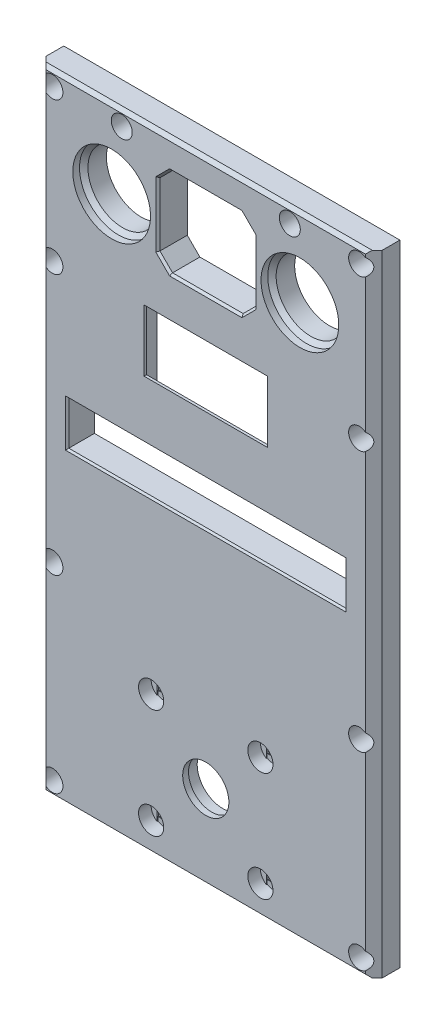
SolidWorks part; units mm, degrees
ref_plane "Front Plane" through (0, 0, 0) normal (0, 0, 1) x (1, 0, 0)
ref_plane "Top Plane" through (0, 0, 0) normal (0, 1, 0) x (1, 0, 0)
ref_plane "Right Plane" through (0, 0, 0) normal (1, 0, 0) x (0, 0, -1)
sketch "Sketch1" plane through (0, 0, 0) normal (0, 0, 1) x (1, 0, 0)
  line L1 (-40, -75) -> (40, -75)
  line L2 (-40, -75) -> (-40, 75)
  line L3 (-40, 75) -> (40, 75)
  line L4 (40, -75) -> (40, 75)
  line L5 (-40, -75) -> (40, 75) construction
  line L6 (-40, 75) -> (40, -75) construction
  line L7 (-33, -68) -> (33, -68)
  line L8 (-33, -68) -> (-33, 68)
  line L9 (-33, 68) -> (33, 68)
  line L10 (33, -68) -> (33, 68)
  line L11 (-33, -68) -> (33, 68) construction
  line L12 (-33, 68) -> (33, -68) construction
  point P0 (0, 0)
  point P6 (0, 0)
  dimension "D1" = 150
  dimension "D2" = 80
  dimension "D3" = 7
  dimension "D4" = 7
extrude "Boss-Extrude1" add sketch "Sketch1" along normal blind 7
sketch "Sketch2" plane through (0, 0, 7) normal (0, 0, 1) x (1, 0, 0)
  line L0 (33, -68) -> (33, 68) construction
  line L1 (-33, -68) -> (33, -68)
  line L2 (-33, -68) -> (-33, -32)
  line L3 (-33, -32) -> (33, -32)
  line L4 (33, -68) -> (33, -32)
  dimension "D1" = 36
extrude "Boss-Extrude2" add sketch "Sketch2" against normal up to surface (7 mm away) up to face at (0, 0, 0)
sketch "Sketch3" plane through (0, 0, 0) normal (0, 0, -1) x (-1, 0, 0)
  line L0 (0, -75) -> (0, -55) construction
  line L1 (40, -75) -> (-40, -75) construction
  circle A0 centre (0, -55) radius 5.5
  dimension "D1" = 11
  dimension "D2" = 20
extrude "Cut-Extrude1" cut sketch "Sketch3" against normal through all
sketch "Sketch4" plane through (0, 0, 0) normal (0, 0, -1) x (-1, 0, 0)
  circle A0 centre (0, -55) radius 6.05
  dimension "D1" = 12.1
extrude "Cut-Extrude2" cut sketch "Sketch4" against normal offset from surface (5.6 mm away) 1.4 up to face at (-5.5, -55, 7)
sketch "Sketch5" plane through (0, 0, 0) normal (0, 0, -1) x (-1, 0, 0)
  circle A0 centre (0, -55) radius 11.1
  dimension "D1" = 22.2
extrude "Cut-Extrude3" cut sketch "Sketch5" against normal offset from surface (3 mm away) 2.6 up to face at (-6.05, -55, 5.6)
sketch "Sketch6" plane through (0, 0, 0) normal (0, 0, -1) x (-1, 0, 0)
  line L1 (-13, -68) -> (13, -68) construction
  line L2 (-13, -68) -> (-13, -42) construction
  line L3 (-13, -42) -> (13, -42) construction
  line L4 (13, -68) -> (13, -42) construction
  line L5 (-13, -68) -> (13, -42) construction
  line L6 (-13, -42) -> (13, -68) construction
  circle A0 centre (-13, -42) radius 1.6
  circle A1 centre (13, -42) radius 1.6
  circle A2 centre (13, -68) radius 1.6
  circle A3 centre (-13, -68) radius 1.6
  point P0 (0, -55)
  dimension "D2" = 3.2
  dimension "D1" = 26
extrude "Cut-Extrude4" cut sketch "Sketch6" against normal through all
sketch "Sketch7" plane through (0, 0, 0) normal (0, 0, -1) x (-1, 0, 0)
  line L1 (-25, -74) -> (25, -74)
  line L2 (-25, -74) -> (-25, -36)
  line L3 (-25, -36) -> (25, -36)
  line L4 (25, -74) -> (25, -36)
  line L5 (-25, -74) -> (25, -36) construction
  line L6 (-25, -36) -> (25, -74) construction
  point P0 (0, -55)
  dimension "D1" = 50
  dimension "D2" = 38
extrude "Cut-Extrude5" cut sketch "Sketch7" against normal blind 1
sketch "Sketch8" plane through (0, 0, 7) normal (0, 0, 1) x (1, 0, 0)
  circle A0 centre (-13, -42) radius 3
  circle A1 centre (13, -42) radius 3
  circle A2 centre (13, -68) radius 3
  circle A3 centre (-13, -68) radius 3
  dimension "D1" = 6
extrude "Cut-Extrude6" cut sketch "Sketch8" against normal blind 3
sketch "Sketch9" plane through (0, 0, 7) normal (0, 0, 1) x (1, 0, 0)
  line L0 (-40, 75) -> (-40, -75) construction
  line L1 (-36.5, -71.5) -> (36.5, -71.5) construction
  line L2 (-36.5, -71.5) -> (-36.5, 71.5) construction
  line L3 (-36.5, 71.5) -> (36.5, 71.5) construction
  line L4 (36.5, -71.5) -> (36.5, 71.5) construction
  line L5 (-36.5, -71.5) -> (36.5, 71.5) construction
  line L6 (-36.5, 71.5) -> (36.5, -71.5) construction
  line L7 (40, 75) -> (-40, 75) construction
  circle A0 centre (-36.5, 71.5) radius 1.35
  circle A1 centre (36.5, 71.5) radius 1.35
  circle A2 centre (36.5, -71.5) radius 1.35
  circle A3 centre (-36.5, -71.5) radius 1.35
  circle A6 centre (-36.5, 35.5) radius 1.35
  circle A7 centre (-36.5, -26.5) radius 1.35
  circle A8 centre (36.5, -26.5) radius 1.35
  circle A9 centre (36.5, 35.5) radius 1.35
  point P0 (0, 0)
  dimension "D3" = 2.7
  dimension "D4" = 45
  dimension "D5" = 36
  dimension "D1" = 3.5
  dimension "D2" = 3.5
extrude "Cut-Extrude7" cut sketch "Sketch9" against normal through all
sketch "Sketch10" plane through (0, 0, 7) normal (0, 0, 1) x (1, 0, 0)
  circle A0 centre (-36.5, 71.5) radius 2.5
  circle A1 centre (36.5, 71.5) radius 2.5
  circle A2 centre (-36.5, 35.5) radius 2.5
  circle A3 centre (-36.5, -26.5) radius 2.5
  circle A4 centre (-36.5, -71.5) radius 2.5
  circle A5 centre (36.5, -71.5) radius 2.5
  circle A6 centre (36.5, 35.5) radius 2.5
  circle A7 centre (36.5, -26.5) radius 2.5
  dimension "D1" = 5
extrude "Cut-Extrude8" cut sketch "Sketch10" against normal blind 5
chamfer "Chamfer1" distance 2 angle 45 2 edges at (-40, 0, 7) (40, 0, 7)
sketch "Sketch11" plane through (0, 0, 7) normal (0, 0, 1) x (1, 0, 0)
  line L0 (33, -32) -> (33, 68) construction
  line L1 (-33, -32) -> (33, -32)
  line L2 (-33, -32) -> (-33, -1.5)
  line L3 (-33, -1.5) -> (33, -1.5)
  line L4 (33, -32) -> (33, -1.5)
  line L5 (-38, -75) -> (38, -75) construction
  dimension "D1" = 73.5
extrude "Boss-Extrude3" add sketch "Sketch11" against normal up to surface (7 mm away) up to face at (37.85, 71.5, 0)
sketch "Sketch12" plane through (0, 0, 2) normal (0, 0, 1) x (1, 0, 0)
  line L2 (-37.85, -73.6042) -> (-37.85, -69.3958)
  line L4 (-35.15, -73.6042) -> (-35.15, -69.3958)
  line L5 (-37.85, -73.6042) -> (-35.15, -69.3958) construction
  line L6 (-37.85, -69.3958) -> (-35.15, -73.6042) construction
  line L8 (-37.85, -28.6042) -> (-37.85, -24.3958)
  line L10 (-35.15, -28.6042) -> (-35.15, -24.3958)
  line L11 (-37.85, -28.6042) -> (-35.15, -24.3958) construction
  line L12 (-37.85, -24.3958) -> (-35.15, -28.6042) construction
  line L14 (-37.85, 33.3958) -> (-37.85, 37.6042)
  line L16 (-35.15, 33.3958) -> (-35.15, 37.6042)
  line L17 (-37.85, 33.3958) -> (-35.15, 37.6042) construction
  line L18 (-37.85, 37.6042) -> (-35.15, 33.3958) construction
  line L20 (-37.85, 69.3958) -> (-37.85, 73.6042)
  line L22 (-35.15, 69.3958) -> (-35.15, 73.6042)
  line L23 (-37.85, 69.3958) -> (-35.15, 73.6042) construction
  line L24 (-37.85, 73.6042) -> (-35.15, 69.3958) construction
  arc A0 (-38, -73.5) -> (-38, -69.5) centre (-36.5, -71.5) ccw construction
  circle A1 centre (-36.5, -26.5) radius 2.5 construction
  circle A2 centre (-36.5, 35.5) radius 2.5 construction
  arc A3 (-38, 69.5) -> (-38, 73.5) centre (-36.5, 71.5) ccw construction
  circle A4 centre (-36.5, 71.5) radius 1.35 construction
  circle A5 centre (-36.5, 71.5) radius 2.5 construction
  arc A6 (-35.15, 73.6042) -> (-37.85, 73.6042) centre (-36.5, 71.5) ccw
  arc A7 (-37.85, 69.3958) -> (-35.15, 69.3958) centre (-36.5, 71.5) ccw
  circle A8 centre (-36.5, 35.5) radius 1.35 construction
  arc A9 (-37.85, 33.3958) -> (-35.15, 33.3958) centre (-36.5, 35.5) ccw
  arc A10 (-35.15, 37.6042) -> (-37.85, 37.6042) centre (-36.5, 35.5) ccw
  circle A11 centre (-36.5, -26.5) radius 1.35 construction
  arc A12 (-37.85, -28.6042) -> (-35.15, -28.6042) centre (-36.5, -26.5) ccw
  arc A13 (-35.15, -24.3958) -> (-37.85, -24.3958) centre (-36.5, -26.5) ccw
  circle A14 centre (-36.5, -71.5) radius 1.35 construction
  arc A16 (-37.85, -73.6042) -> (-35.15, -73.6042) centre (-36.5, -71.5) ccw
  arc A18 (-35.15, -69.3958) -> (-37.85, -69.3958) centre (-36.5, -71.5) ccw
  point P0 (-36.5, -71.5)
  point P9 (-36.5, -26.5)
  point P17 (-36.5, 35.5)
  point P25 (-36.5, 71.5)
extrude "Cut-Extrude9" cut sketch "Sketch12" against normal blind 0.2
sketch "Sketch13" plane through (0, 0, 1.8) normal (0, 0, 1) x (1, 0, 0)
  line L0 (-35.15, -71.5) -> (-35.15, -69.3958) construction
  line L1 (-37.85, -72.85) -> (-35.15, -72.85)
  line L2 (-37.85, -72.85) -> (-37.85, -70.15)
  line L3 (-37.85, -70.15) -> (-35.15, -70.15)
  line L4 (-35.15, -72.85) -> (-35.15, -70.15)
  line L5 (-37.85, -72.85) -> (-35.15, -70.15) construction
  line L6 (-37.85, -70.15) -> (-35.15, -72.85) construction
  line L7 (-35.15, -26.5) -> (-35.15, -24.3958) construction
  line L8 (-37.85, -27.85) -> (-35.15, -27.85)
  line L9 (-37.85, -27.85) -> (-37.85, -25.15)
  line L10 (-37.85, -25.15) -> (-35.15, -25.15)
  line L11 (-35.15, -27.85) -> (-35.15, -25.15)
  line L12 (-37.85, -27.85) -> (-35.15, -25.15) construction
  line L13 (-37.85, -25.15) -> (-35.15, -27.85) construction
  line L14 (-35.15, 33.3958) -> (-35.15, 37.6042) construction
  line L15 (-37.85, 34.15) -> (-35.15, 34.15)
  line L16 (-37.85, 34.15) -> (-37.85, 36.85)
  line L17 (-37.85, 36.85) -> (-35.15, 36.85)
  line L18 (-35.15, 34.15) -> (-35.15, 36.85)
  line L19 (-37.85, 34.15) -> (-35.15, 36.85) construction
  line L20 (-37.85, 36.85) -> (-35.15, 34.15) construction
  line L21 (-35.15, 69.3958) -> (-35.15, 73.6042) construction
  line L22 (-37.85, 70.15) -> (-35.15, 70.15)
  line L23 (-37.85, 70.15) -> (-37.85, 72.85)
  line L24 (-37.85, 72.85) -> (-35.15, 72.85)
  line L25 (-35.15, 70.15) -> (-35.15, 72.85)
  line L26 (-37.85, 70.15) -> (-35.15, 72.85) construction
  line L27 (-37.85, 72.85) -> (-35.15, 70.15) construction
  arc A0 (-35.15, -71.5) -> (-37.85, -71.5) centre (-36.5, -71.5) ccw construction
  arc A1 (-35.15, -26.5) -> (-37.85, -26.5) centre (-36.5, -26.5) ccw construction
  arc A2 (-35.15, 35.5) -> (-37.85, 35.5) centre (-36.5, 35.5) ccw construction
  arc A3 (-35.15, 71.5) -> (-37.85, 71.5) centre (-36.5, 71.5) ccw construction
  point P0 (-36.5, -71.5)
  point P11 (-36.5, -26.5)
  point P22 (-36.5, 35.5)
  point P33 (-36.5, 71.5)
extrude "Cut-Extrude10" cut sketch "Sketch13" against normal blind 0.2
sketch "Sketch14" plane through (0, 0, 4) normal (0, 0, 1) x (1, 0, 0)
  line L2 (-14.6, -44.5377) -> (-14.6, -39.4623)
  line L4 (-11.4, -44.5377) -> (-11.4, -39.4623)
  line L5 (-14.6, -44.5377) -> (-11.4, -39.4623) construction
  line L6 (-14.6, -39.4623) -> (-11.4, -44.5377) construction
  line L8 (-14.6, -70.5377) -> (-14.6, -65.4623)
  line L10 (-11.4, -70.5377) -> (-11.4, -65.4623)
  line L11 (-14.6, -70.5377) -> (-11.4, -65.4623) construction
  line L12 (-14.6, -65.4623) -> (-11.4, -70.5377) construction
  circle A0 centre (-13, -42) radius 3 construction
  circle A1 centre (-13, -68) radius 3 construction
  circle A2 centre (-13, -42) radius 3 construction
  arc A3 (-14.6, -44.5377) -> (-11.4, -44.5377) centre (-13, -42) ccw
  arc A4 (-14.6, -70.5377) -> (-11.4, -70.5377) centre (-13, -68) ccw
  circle A5 centre (-13, -42) radius 1.6 construction
  circle A6 centre (-13, -68) radius 1.6 construction
  arc A7 (-11.4, -39.4623) -> (-14.6, -39.4623) centre (-13, -42) ccw
  arc A8 (-11.4, -65.4623) -> (-14.6, -65.4623) centre (-13, -68) ccw
  point P0 (-13, -42)
  point P8 (-13, -68)
extrude "Cut-Extrude11" cut sketch "Sketch14" against normal blind 0.2
sketch "Sketch15" plane through (0, 0, 3.8) normal (0, 0, 1) x (1, 0, 0)
  line L0 (-11.4, -42) -> (-11.4, -39.4623) construction
  line L1 (-14.6, -43.6) -> (-11.4, -43.6)
  line L2 (-14.6, -43.6) -> (-14.6, -40.4)
  line L3 (-14.6, -40.4) -> (-11.4, -40.4)
  line L4 (-11.4, -43.6) -> (-11.4, -40.4)
  line L5 (-14.6, -43.6) -> (-11.4, -40.4) construction
  line L6 (-14.6, -40.4) -> (-11.4, -43.6) construction
  line L7 (-11.4, -68) -> (-11.4, -65.4623) construction
  line L8 (-14.6, -69.6) -> (-11.4, -69.6)
  line L9 (-14.6, -69.6) -> (-14.6, -66.4)
  line L10 (-14.6, -66.4) -> (-11.4, -66.4)
  line L11 (-11.4, -69.6) -> (-11.4, -66.4)
  line L12 (-14.6, -69.6) -> (-11.4, -66.4) construction
  line L13 (-14.6, -66.4) -> (-11.4, -69.6) construction
  arc A0 (-11.4, -68) -> (-14.6, -68) centre (-13, -68) ccw construction
  arc A1 (-14.6, -42) -> (-11.4, -42) centre (-13, -42) ccw construction
  point P0 (-13, -42)
  point P8 (-13, -68)
extrude "Cut-Extrude12" cut sketch "Sketch15" against normal blind 0.2
mirror "Mirror1" about plane through (0, 0, 0) normal (1, 0, 0) of "Cut-Extrude10", "Cut-Extrude11", "Cut-Extrude12", "Cut-Extrude9"
chamfer "Chamfer2" distance 0.4 angle 45 4 edges at (33, 33.25, 7) (0, 68, 7) (0, -1.5, 7) (-33, 33.25, 7)
chamfer "Chamfer3" distance 0.8 angle 45 6 edges at (-40, 0, 0) (40, 0, 0) (0, -75, 7) (0, 75, 7) (0, -75, 0) (0, 75, 0)
sketch "Sketch16" plane through (0, 0, 0) normal (1, 0, 0) x (0, 0, -1)
  line L0 (0, -4) -> (0, -15.4)
  line L1 (0, 74.2) -> (0, -74.2) construction
  line L2 (0, -15.4) -> (3.2, -12.2)
  line L3 (3.2, -12.2) -> (3.2, -7.2)
  line L4 (3.2, -7.2) -> (0, -4)
  line L5 (0, -15.4) -> (0, -19.4) construction
  line L6 (0.6, -7.7) -> (2.6, -7.7)
  line L7 (0.6, -7.7) -> (0.6, -11.7)
  line L8 (0.6, -11.7) -> (2.6, -11.7)
  line L9 (2.6, -7.7) -> (2.6, -11.7)
  line L10 (-1.046, -17.4) -> (12.8392, -17.4) construction
  line L11 (2.6, -27.1) -> (2.6, -23.1)
  line L12 (0.6, -23.1) -> (2.6, -23.1)
  line L13 (0.6, -27.1) -> (0.6, -23.1)
  line L14 (0.6, -27.1) -> (2.6, -27.1)
  line L15 (3.2, -27.6) -> (0, -30.8)
  line L16 (3.2, -22.6) -> (3.2, -27.6)
  line L17 (0, -19.4) -> (3.2, -22.6)
  line L18 (0, -30.8) -> (0, -19.4)
  point P10 (2.6, -9.7)
  point P11 (3.2, -9.7)
  point P24 (0, -17.4)
  dimension "D1" = 5
  dimension "D2" = 2
  dimension "D3" = 0.6
  dimension "D4" = 0.6
  dimension "D5" = 45
  dimension "D6" = 4
  dimension "D7" = 4
  dimension "D8" = 4
extrude "Boss-Extrude4" add sketch "Sketch16" along normal mid plane 2
pattern_linear "LPattern1" count 2 spacing 20 along (1, 0, 0) count 2 spacing 20 along (-1, 0, 0) of "Boss-Extrude4"
sketch "Sketch17" plane through (0, 0, 0) normal (0, 0, -1) x (-1, 0, 0)
  line L0 (-20, 71.5) -> (20, 71.5) construction
  line L1 (-39.2, 75) -> (39.2, 75) construction
  circle A0 centre (-36.5, 71.5) radius 1.35 construction
  circle A1 centre (-36.5, 71.5) radius 1.35 construction
  circle A2 centre (-20, 71.5) radius 1.35
  circle A3 centre (20, 71.5) radius 1.35
  point P3 (0, 71.5)
  point P6 (0, 75)
  dimension "D1" = 40
extrude "Cut-Extrude13" cut sketch "Sketch17" against normal through all
sketch "Sketch18" plane through (0, 0, 7) normal (0, 0, 1) x (1, 0, 0)
  circle A0 centre (-20, 71.5) radius 2.5
  circle A1 centre (20, 71.5) radius 2.5
  arc A2 (-38, 69.5) -> (-38, 73.5) centre (-36.5, 71.5) ccw construction
extrude "Cut-Extrude14" cut sketch "Sketch18" against normal up to surface (5 mm away) up to face at (34.575, 71.5, 2)
sketch "Sketch19" plane through (0, 0, 2) normal (0, 0, 1) x (1, 0, 0)
  line L2 (-21.35, 69.3958) -> (-21.35, 73.6042)
  line L4 (-18.65, 69.3958) -> (-18.65, 73.6042)
  line L5 (-21.35, 69.3958) -> (-18.65, 73.6042) construction
  line L6 (-21.35, 73.6042) -> (-18.65, 69.3958) construction
  line L8 (18.65, 69.3958) -> (18.65, 73.6042)
  line L10 (21.35, 69.3958) -> (21.35, 73.6042)
  line L11 (18.65, 69.3958) -> (21.35, 73.6042) construction
  line L12 (18.65, 73.6042) -> (21.35, 69.3958) construction
  circle A0 centre (-20, 71.5) radius 2.5 construction
  circle A1 centre (20, 71.5) radius 2.5 construction
  circle A2 centre (20, 71.5) radius 1.35 construction
  circle A3 centre (-20, 71.5) radius 1.35 construction
  circle A4 centre (-20, 71.5) radius 2.5 construction
  arc A5 (18.65, 69.3958) -> (21.35, 69.3958) centre (20, 71.5) ccw
  arc A6 (-18.65, 73.6042) -> (-21.35, 73.6042) centre (-20, 71.5) ccw
  arc A7 (21.35, 73.6042) -> (18.65, 73.6042) centre (20, 71.5) ccw
  arc A8 (-21.35, 69.3958) -> (-18.65, 69.3958) centre (-20, 71.5) ccw
  point P0 (-20, 71.5)
  point P8 (20, 71.5)
extrude "Cut-Extrude15" cut sketch "Sketch19" against normal blind 0.2
sketch "Sketch20" plane through (0, 0, 1.8) normal (0, 0, 1) x (1, 0, 0)
  line L0 (-18.65, 69.3958) -> (-18.65, 73.6042) construction
  line L1 (-21.35, 70.15) -> (-18.65, 70.15)
  line L2 (-21.35, 70.15) -> (-21.35, 72.85)
  line L3 (-21.35, 72.85) -> (-18.65, 72.85)
  line L4 (-18.65, 70.15) -> (-18.65, 72.85)
  line L5 (-21.35, 70.15) -> (-18.65, 72.85) construction
  line L6 (-21.35, 72.85) -> (-18.65, 70.15) construction
  line L7 (21.35, 71.5) -> (21.35, 73.6042) construction
  line L8 (18.65, 70.15) -> (21.35, 70.15)
  line L9 (18.65, 70.15) -> (18.65, 72.85)
  line L10 (18.65, 72.85) -> (21.35, 72.85)
  line L11 (21.35, 70.15) -> (21.35, 72.85)
  line L12 (18.65, 70.15) -> (21.35, 72.85) construction
  line L13 (18.65, 72.85) -> (21.35, 70.15) construction
  arc A0 (18.65, 71.5) -> (21.35, 71.5) centre (20, 71.5) ccw construction
  point P0 (-20, 71.5)
  point P8 (20, 71.5)
extrude "Cut-Extrude16" cut sketch "Sketch20" against normal blind 0.2
sketch "Skizze4" plane through (0, 0, 0) normal (0, 0, -1) x (-1, 0, 0)
  line L1 (21, -4) -> (-21, -4)
  line L2 (21, -4) -> (21, -30.8)
  line L3 (21, -30.8) -> (-21, -30.8)
  line L4 (-21, -4) -> (-21, -30.8)
extrude "Schnitt-Linear austragen1" cut sketch "Skizze4" along normal up to surface (3.2 mm away) up to face at (-20, -9.7, -3.2)
sketch "Skizze6" plane through (0, 0, 7) normal (0, 0, 1) x (1, 0, 0)
  line L0 (11.4, 68.4) -> (33.4, 46.4) construction
  line L1 (33.4, 68.4) -> (11.4, 68.4)
  line L2 (33.4, 68.4) -> (33.4, 46.4)
  line L3 (33.4, 46.4) -> (11.4, 46.4)
  line L4 (11.4, 68.4) -> (11.4, 46.4)
  line L5 (22.4, 68.4) -> (22.4, 46.4) construction
  circle A0 centre (22.4, 56.4) radius 8.25
  point P10 (22.4, 57.4)
  dimension "D1" = 16.5
  dimension "D2" = 22
  dimension "D3" = 22
  dimension "D4" = 1
extrude "Aufsatz-Linear austragen1" add sketch "Skizze6" against normal up to surface (7 mm away) up to face at (18.65, 71.5, 0)
sketch "Skizze7" plane through (0, 0, 7) normal (0, 0, 1) x (1, 0, 0)
  circle A0 centre (22.4, 56.4) radius 9.25
  dimension "D1" = 18.5
extrude "Schnitt-Linear austragen2" cut sketch "Skizze7" against normal blind 1.6
chamfer "Fase6" distance 0.5 angle 45 2 edges at (11.4, 57.4, 7) (22.4, 46.4, 7)
chamfer "Fase7" distance 4 angle 45 1 edges at (11.4, 46.4, 3.25)
chamfer "Fase8" distance 1 angle 45 1 edges at (30.65, 56.4, 5.4)
mirror "Mirror2" about plane through (0, 0, 0) normal (1, 0, 0) of "Fase6", "Schnitt-Linear austragen2", "Fase8", "Aufsatz-Linear austragen1", "Fase7"
sketch "Sketch21" plane through (0, 0, 7) normal (0, 0, 1) x (1, 0, 0)
  line L0 (33.4, 46.9) -> (33.4, -1.9) construction
  line L1 (-33.4, 46.9) -> (-14.9, 46.9)
  line L2 (-33.4, 46.9) -> (-33.4, 8.9)
  line L3 (-33.4, 8.9) -> (33.4, 8.9)
  line L4 (33.4, 46.9) -> (33.4, 8.9)
  line L5 (-14.9, 46.9) -> (-11.4, 50.4)
  line L6 (-11.4, 50.4) -> (-11.4, 46.9)
  line L7 (11.4, 50.4) -> (14.9, 46.9)
  line L8 (11.4, 50.4) -> (11.4, 46.9)
  line L9 (-11.4, 46.9) -> (11.4, 46.9)
  line L10 (14.9, 46.9) -> (33.4, 46.9)
  dimension "D1" = 38
extrude "Boss-Extrude5" add sketch "Sketch21" against normal up to surface (7 mm away) up to face at (0, 41.94, 0)
chamfer "Chamfer4" distance 0.5 angle 45 3 edges at (11.4, 48.65, 7) (-11.4, 48.65, 7) (0, 46.9, 7)
sketch "Sketch22" plane through (0, 0, 0) normal (0, 0, -1) x (-1, 0, 0)
  line L0 (0, 46.9) -> (0, 8.9) construction
  line L1 (-11.4, 46.9) -> (11.4, 46.9) construction
  line L2 (33, 8.9) -> (-33, 8.9) construction
  line L4 (-17.8, 11.05) -> (17.8, 11.05) construction
  line L5 (-17.8, 11.05) -> (-17.8, 44.75) construction
  line L6 (-17.8, 44.75) -> (17.8, 44.75) construction
  line L7 (17.8, 11.05) -> (17.8, 44.75) construction
  line L8 (-17.8, 11.05) -> (17.8, 44.75) construction
  line L9 (-17.8, 44.75) -> (17.8, 11.05) construction
  line L10 (-15.2, 13.65) -> (15.2, 13.65) construction
  line L11 (-15.2, 13.65) -> (-15.2, 42.15) construction
  line L12 (-15.2, 42.15) -> (15.2, 42.15) construction
  line L13 (15.2, 13.65) -> (15.2, 42.15) construction
  line L14 (-15.2, 13.65) -> (15.2, 42.15) construction
  line L15 (-15.2, 42.15) -> (15.2, 13.65) construction
  line L16 (-18.05, 10.8) -> (18.05, 10.8)
  line L17 (-18.05, 10.8) -> (-18.05, 45)
  line L18 (-18.05, 45) -> (18.05, 45)
  line L19 (18.05, 10.8) -> (18.05, 45)
  line L20 (-18.05, 10.8) -> (18.05, 45) construction
  line L21 (-18.05, 45) -> (18.05, 10.8) construction
  line L22 (-14.71, 22.7) -> (14.71, 22.7) construction
  line L23 (-14.71, 22.7) -> (-14.71, 37.4) construction
  line L24 (-14.71, 37.4) -> (14.71, 37.4) construction
  line L25 (14.71, 22.7) -> (14.71, 37.4) construction
  line L26 (-14.71, 22.7) -> (14.71, 37.4) construction
  line L27 (-14.71, 37.4) -> (14.71, 22.7) construction
  circle A0 centre (-15.2, 42.15) radius 1.5 construction
  circle A1 centre (15.2, 42.15) radius 1.5 construction
  circle A2 centre (15.2, 13.65) radius 1.5 construction
  circle A3 centre (-15.2, 13.65) radius 1.5 construction
  point P6 (0, 27.9)
  point P11 (0, 27.9)
  point P20 (0, 27.9)
  point P25 (0, 30.05)
  dimension "D5" = 3
  dimension "D1" = 35.6
  dimension "D2" = 33.7
  dimension "D3" = 30.4
  dimension "D4" = 28.5
  dimension "D6" = 0.25
  dimension "D7" = 0.25
  dimension "D8" = 14.7
  dimension "D9" = 29.42
  dimension "D10" = 7.35
chamfer "Chamfer5" distance 0.4 angle 45 1 edges at (0, 8.9, 7)
sketch "Sketch24" plane through (0, 0, 7) normal (0, 0, 1) x (1, 0, 0)
  line L1 (-11.9, 68.4) -> (11.9, 68.4)
  line L2 (-11.9, 68.4) -> (-11.9, 46.4)
  line L3 (-11.9, 46.4) -> (11.9, 46.4)
  line L4 (11.9, 68.4) -> (11.9, 46.4)
  line L5 (-11.4, 68) -> (11.4, 68)
  line L6 (-11.4, 68) -> (-11.4, 46.9)
  line L7 (-11.4, 46.9) -> (11.4, 46.9)
  line L8 (11.4, 68) -> (11.4, 46.9)
extrude "Boss-Extrude6" add sketch "Sketch24" against normal up to vertex (0.5 mm away) up to point (11.4, 46.9, 6.5)
chamfer "Chamfer7" distance 3 angle 45 4 edges at (11.4, 46.9, 3.5) (11.4, 68, 3.5) (-11.4, 68, 3.5) (-11.4, 46.9, 3.5)
chamfer "Chamfer8" distance 0.5 angle 45 8 edges at (-9.9, 48.4, 7) (0, 46.9, 7) (9.9, 48.4, 7) (11.4, 57.45, 7) (9.9, 66.5, 7) (0, 68, 7) (-9.9, 66.5, 7) (-11.4, 57.45, 7)
extrude "Cut-Extrude17" cut sketch "Sketch22" against normal offset from surface (6.4 mm away) 0.6 up to face at (0, 57.45, 7)
sketch "Sketch26" plane through (0, 0, 6.4) normal (0, 0, -1) x (-1, 0, 0)
  line L0 (14.71, 22.7) -> (14.71, 37.4) construction
  line L1 (-14.71, 22.7) -> (14.71, 22.7) construction
  line L2 (-14.71, 22.7) -> (-14.71, 37.4) construction
  line L3 (-14.71, 37.4) -> (14.71, 37.4) construction
  line L4 (14.71, 22.7) -> (14.71, 37.4)
  line L5 (-14.71, 22.7) -> (14.71, 22.7)
  line L6 (-14.71, 22.7) -> (-14.71, 37.4)
  line L7 (-14.71, 37.4) -> (14.71, 37.4)
extrude "Cut-Extrude18" cut sketch "Sketch26" against normal through all
sketch "Sketch27" plane through (0, 0, 6.4) normal (0, 0, -1) x (-1, 0, 0)
  line L0 (-17.8, 11.05) -> (17.8, 44.75) construction
  line L1 (18.05, 45) -> (12.7822, 45)
  line L2 (18.05, 45) -> (18.05, 40)
  line L3 (18.05, 40) -> (12.7822, 40)
  line L4 (12.7822, 45) -> (12.7822, 40)
  line L5 (-17.8, 44.75) -> (17.8, 11.05) construction
  line L6 (-18.05, 45) -> (-12.7822, 45)
  line L7 (-18.05, 45) -> (-18.05, 40)
  line L8 (-18.05, 40) -> (-12.7822, 40)
  line L9 (-12.7822, 45) -> (-12.7822, 40)
  line L10 (-15.2, 13.65) -> (15.2, 42.15) construction
  line L11 (-18.05, 10.8) -> (-12.9067, 10.8)
  line L12 (-18.05, 10.8) -> (-18.05, 15.8)
  line L13 (-18.05, 15.8) -> (-12.9067, 15.8)
  line L14 (-12.9067, 10.8) -> (-12.9067, 15.8)
  line L16 (18.05, 10.8) -> (12.7822, 10.8)
  line L17 (18.05, 10.8) -> (18.05, 15.8)
  line L18 (18.05, 15.8) -> (12.7822, 15.8)
  line L19 (12.7822, 10.8) -> (12.7822, 15.8)
  dimension "D1" = 5
extrude "Boss-Extrude7" add sketch "Sketch27" along normal blind 1.6
chamfer "Chamfer9" distance 0.5 angle 45 8 edges at (0, 45, 0) (18.05, 27.9, 0) (0, 10.8, 0) (-18.05, 27.9, 0) (33, 3.7, 0) (0, -1.5, 0) (-33, 3.7, 0) (0, 8.9, 0)
